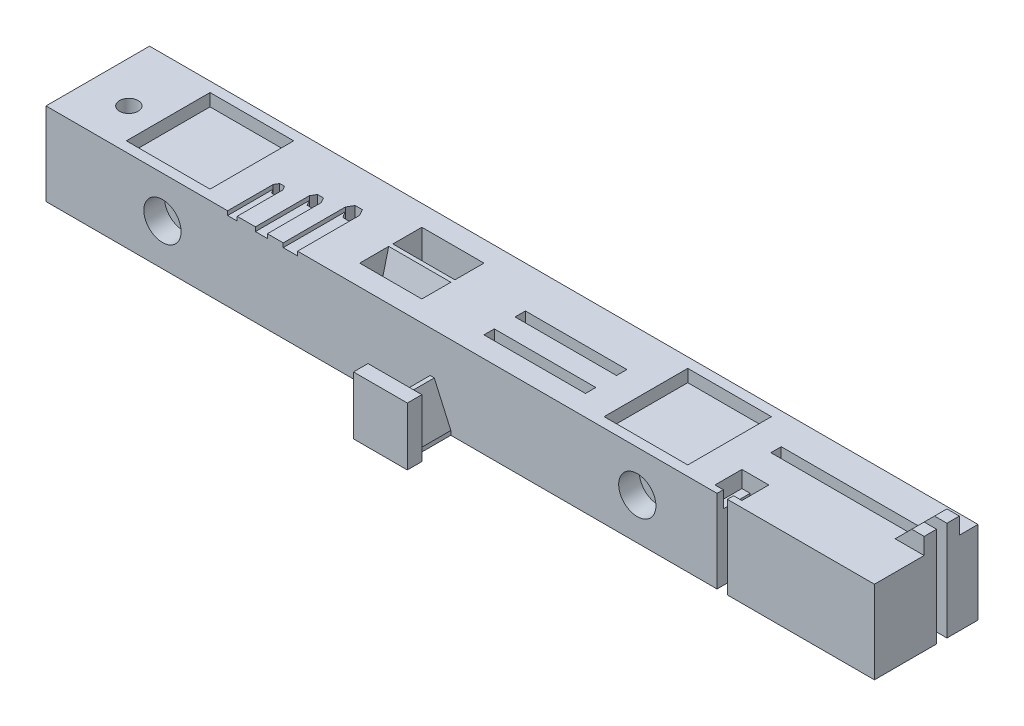
SolidWorks part; units mm, degrees
ref_plane "Piano frontale" through (0, 0, 0) normal (0, 0, 1) x (1, 0, 0)
ref_plane "Piano superiore" through (0, 0, 0) normal (0, 1, 0) x (1, 0, 0)
ref_plane "Piano destro" through (0, 0, 0) normal (1, 0, 0) x (0, 0, -1)
sketch "Schizzo1" plane through (0, 0, 0) normal (0, 0, 1) x (1, 0, 0)
  line L1 (-63.299, 14.3184) -> (136.701, 14.3184)
  line L2 (-63.299, 14.3184) -> (-63.299, -5.6816)
  line L3 (-63.299, -5.6816) -> (136.701, -5.6816)
  line L4 (136.701, 14.3184) -> (136.701, -5.6816)
  dimension "D1" = 20
  dimension "D2" = 200
extrude "Estrusione-Estrusione1" add sketch "Schizzo1" along normal blind 25
sketch "Schizzo2" plane through (0, 14.3184, 0) normal (0, 1, 0) x (1, 0, 0)
  line L0 (136.701, 0) -> (-63.299, 0) construction
  line L1 (136.701, -25) -> (-63.299, -25) construction
  line L2 (-63.299, -25) -> (-63.299, 0) construction
  line L3 (-18.8763, -15) -> (-17.7216, -15)
  line L4 (-17.7216, -15) -> (-17.1443, -14)
  line L5 (-17.1443, -14) -> (-17.7216, -13)
  line L6 (-17.7216, -13) -> (-18.8763, -13)
  line L7 (-18.8763, -13) -> (-19.4537, -14)
  line L8 (-19.4537, -14) -> (-18.8763, -15)
  line L9 (-9.8556, -12) -> (-10.5773, -10.75)
  line L10 (-10.5773, -10.75) -> (-12.0207, -10.75)
  line L11 (-12.0207, -10.75) -> (-12.7423, -12)
  line L12 (-12.7423, -12) -> (-12.0207, -13.25)
  line L13 (-12.0207, -13.25) -> (-10.5773, -13.25)
  line L14 (-10.5773, -13.25) -> (-9.8556, -12)
  line L15 (-3.4329, -11.5) -> (-2.5669, -10)
  line L16 (-2.5669, -10) -> (-3.4329, -8.5)
  line L17 (-3.4329, -8.5) -> (-5.165, -8.5)
  line L18 (-5.165, -8.5) -> (-6.031, -10)
  line L19 (-6.031, -10) -> (-5.165, -11.5)
  line L20 (-5.165, -11.5) -> (-3.4329, -11.5)
  circle A0 centre (-53.299, -15) radius 2.25
  circle A1 centre (-18.299, -14) radius 1 construction
  circle A2 centre (-11.299, -12) radius 1.25 construction
  circle A3 centre (-4.299, -10) radius 1.5 construction
  dimension "D2" = 4.5
  dimension "D4" = 2
  dimension "D5" = 2.5
  dimension "D6" = 3
  dimension "D1" = 15
  dimension "D3" = 10
  dimension "D7" = 35
  dimension "D8" = 7
  dimension "D9" = 7
  dimension "D10" = 11
  dimension "D11" = 13
  dimension "D12" = 15
extrude "Taglio-Estrusione1" cut sketch "Schizzo2" against normal through all
sketch "Schizzo4" plane through (0, 14.3184, 0) normal (0, 1, 0) x (1, 0, 0)
  line L0 (136.701, -25) -> (-63.299, -25) construction
  line L1 (-19.4537, -14) -> (-17.1443, -14)
  line L2 (-19.4537, -14) -> (-19.4537, -25)
  line L3 (-19.4537, -25) -> (-17.1443, -25)
  line L4 (-17.1443, -14) -> (-17.1443, -25)
  line L5 (-12.7423, -12) -> (-9.8556, -12)
  line L6 (-12.7423, -12) -> (-12.7423, -25)
  line L7 (-12.7423, -25) -> (-9.8556, -25)
  line L8 (-9.8556, -12) -> (-9.8556, -25)
  line L10 (-6.031, -10) -> (-2.5669, -10)
  line L11 (-6.031, -10) -> (-6.031, -25)
  line L12 (-6.031, -25) -> (-2.5669, -25)
  line L13 (-2.5669, -10) -> (-2.5669, -25)
extrude "Taglio-Estrusione2" cut sketch "Schizzo4" against normal blind 1
sketch "Schizzo7" plane through (0, 14.3184, 0) normal (0, 1, 0) x (1, 0, 0)
  line L0 (136.701, -25) -> (-2.5669, -25) construction
  line L1 (7.4331, -14.5) -> (22.4331, -14.5)
  line L2 (7.4331, -14.5) -> (7.4331, -20)
  line L3 (7.4331, -20) -> (22.4331, -20)
  line L4 (22.4331, -14.5) -> (22.4331, -20)
  line L5 (7.4331, -5) -> (22.4331, -5)
  line L6 (7.4331, -5) -> (7.4331, -10.5)
  line L7 (7.4331, -10.5) -> (22.4331, -10.5)
  line L8 (22.4331, -5) -> (22.4331, -10.5)
  dimension "D1" = 15
  dimension "D2" = 15
  dimension "D3" = 15
  dimension "D4" = 4
  dimension "D5" = 5.5
  dimension "D6" = 5
  dimension "D7" = 10
extrude "Taglio-Estrusione3" cut sketch "Schizzo7" against normal through all
chamfer "Smusso1" distance 1.5 distance2 6 2 edges at (14.9331, 14.3184, 14.5) (14.9331, 14.3184, 10.5) first distance on face at (14.9331, 14.3184, 7.75)
sketch "Schizzo8" plane through (0, 14.3184, 0) normal (0, 1, 0) x (1, 0, 0)
  line L0 (7.4331, -20) -> (22.4331, -20) construction
  line L1 (37.4331, -17.5) -> (61.9331, -17.5)
  line L2 (37.4331, -17.5) -> (37.4331, -20)
  line L3 (37.4331, -20) -> (61.9331, -20)
  line L4 (61.9331, -17.5) -> (61.9331, -20)
  line L5 (37.4331, -10) -> (61.9331, -10)
  line L6 (37.4331, -10) -> (37.4331, -12.5)
  line L7 (37.4331, -12.5) -> (61.9331, -12.5)
  line L8 (61.9331, -10) -> (61.9331, -12.5)
  line L9 (22.4331, -12) -> (22.4331, -5) construction
  point P10 (22.4331, -8.5)
  dimension "D1" = 24.5
  dimension "D2" = 24.5
  dimension "D3" = 2.5
  dimension "D4" = 2.5
  dimension "D5" = 5
  dimension "D6" = 15
extrude "Taglio-Estrusione4" cut sketch "Schizzo8" against normal blind 15
sketch "Schizzo9" plane through (0, 14.3184, 0) normal (0, 1, 0) x (1, 0, 0)
  line L0 (136.701, -25) -> (136.701, 0) construction
  line L1 (96.701, -7.5) -> (136.701, -7.5)
  line L2 (96.701, -7.5) -> (96.701, -10)
  line L3 (96.701, -10) -> (136.701, -10)
  line L4 (136.701, -7.5) -> (136.701, -10)
  line L5 (136.701, 0) -> (-63.299, 0) construction
  dimension "D1" = 40
  dimension "D2" = 2.5
  dimension "D3" = 7.5
extrude "Taglio-Estrusione5" cut sketch "Schizzo9" against normal through all
sketch "Schizzo10" plane through (0, 14.3184, 0) normal (0, 1, 0) x (1, 0, 0)
  line L1 (136.701, -7.5) -> (129.701, -7.5)
  line L2 (136.701, -7.5) -> (136.701, -4.5)
  line L3 (136.701, -4.5) -> (129.701, -4.5)
  line L4 (129.701, -7.5) -> (129.701, -4.5)
  line L5 (136.701, -10) -> (129.701, -10)
  line L6 (136.701, -10) -> (136.701, -13)
  line L7 (136.701, -13) -> (129.701, -13)
  line L8 (129.701, -10) -> (129.701, -13)
  dimension "D1" = 7
  dimension "D2" = 7
  dimension "D3" = 3
  dimension "D4" = 3
extrude "Estrusione-Estrusione5" add sketch "Schizzo10" along normal blind 4
chamfer "Smusso2" distance 4 angle 45 2 edges at (129.701, 18.3184, 11.5) (129.701, 18.3184, 6)
sketch "Schizzo11" plane through (0, 14.3184, 0) normal (0, 1, 0) x (1, 0, 0)
  line L0 (136.701, -25) -> (-2.5669, -25) construction
  line L1 (98.701, -25) -> (101.201, -25)
  line L2 (98.701, -25) -> (98.701, -17)
  line L3 (98.701, -17) -> (101.201, -17)
  line L4 (101.201, -25) -> (101.201, -17)
  line L5 (96.701, -7.5) -> (96.701, -10) construction
  dimension "D1" = 2.5
  dimension "D2" = 8
  dimension "D3" = 2
extrude "Taglio-Estrusione6" cut sketch "Schizzo11" against normal through all
sketch "Schizzo12" plane through (0, 14.3184, 0) normal (0, 1, 0) x (1, 0, 0)
  line L0 (101.201, -17) -> (98.701, -17) construction
  line L1 (96.701, -17) -> (103.201, -17)
  line L2 (96.701, -17) -> (96.701, -23.5)
  line L3 (96.701, -23.5) -> (103.201, -23.5)
  line L4 (103.201, -17) -> (103.201, -23.5)
  line L7 (96.701, -7.5) -> (96.701, -10) construction
  dimension "D1" = 6.5
  dimension "D2" = 6.5
extrude "Taglio-Estrusione7" cut sketch "Schizzo12" against normal blind 4
sketch "Schizzo13" plane through (0, 0, 25) normal (0, 0, 1) x (1, 0, 0)
  line L0 (-63.299, -5.6816) -> (98.701, -5.6816) construction
  line L1 (25.4331, 4.3184) -> (34.4331, 4.3184)
  line L2 (25.4331, 4.3184) -> (25.4331, -5.6816)
  line L3 (25.4331, -5.6816) -> (34.4331, -5.6816)
  line L4 (34.4331, 4.3184) -> (34.4331, -5.6816)
  dimension "D1" = 10
  dimension "D2" = 3
  dimension "D3" = 9
extrude "Estrusione-Estrusione9" add sketch "Schizzo13" along normal blind 9 contours L2 L3 L4 L1
sketch "Schizzo14" plane through (0, 0, 34) normal (0, 0, 1) x (1, 0, 0)
  line L0 (25.4331, -5.6816) -> (34.4331, -5.6816) construction
  line L1 (23.4331, 8.3184) -> (36.4331, 8.3184)
  line L2 (23.4331, 8.3184) -> (23.4331, -5.6816)
  line L3 (23.4331, -5.6816) -> (36.4331, -5.6816)
  line L4 (36.4331, 8.3184) -> (36.4331, -5.6816)
  line L5 (25.4331, 4.3184) -> (25.4331, -5.6816) construction
  dimension "D1" = 13
  dimension "D2" = 14
  dimension "D3" = 2
extrude "Estrusione-Estrusione10" add sketch "Schizzo14" along normal blind 3.5
chamfer "Smusso3" distance 9 distance2 4 1 edges at (34.4331, 4.3184, 29.5) first distance on face at (34.4331, 0.5684, 30.625)
chamfer "Smusso4" distance 4 distance2 9 1 edges at (25.4331, 4.3184, 29.5) first distance on face at (27.9331, 4.3184, 29.5)
sketch "Schizzo16" plane through (0, 0, 25) normal (0, 0, 1) x (1, 0, 0)
  line L2 (-19.4537, 14.3184) -> (-63.299, 14.3184) construction
  line L3 (98.701, 14.3184) -> (-2.5669, 14.3184) construction
  circle A0 centre (-35.179, 4.3184) radius 2.25
  circle A1 centre (79.451, 4.3184) radius 2.25
  dimension "D3" = 4.5
  dimension "D4" = 4.5
  dimension "D1" = 17.25
  dimension "D2" = 15.87
  dimension "D5" = 10
  dimension "D6" = 10
extrude "Taglio-Estrusione8" cut sketch "Schizzo16" against normal through all
sketch "Schizzo17" plane through (0, 0, 25) normal (0, 0, 1) x (1, 0, 0)
  circle A0 centre (-35.179, 4.3184) radius 4.5
  circle A1 centre (79.451, 4.3184) radius 4.5
  dimension "D1" = 9
  dimension "D2" = 9
extrude "Taglio-Estrusione9" cut sketch "Schizzo17" against normal blind 5
sketch "Schizzo18" plane through (0, 14.3184, 0) normal (0, 1, 0) x (1, 0, 0)
  line L0 (136.701, 0) -> (-63.299, 0) construction
  line L1 (69.0331, -2.4) -> (89.2331, -2.4)
  line L2 (69.0331, -2.4) -> (69.0331, -22.6)
  line L3 (69.0331, -22.6) -> (89.2331, -22.6)
  line L4 (89.2331, -2.4) -> (89.2331, -22.6)
  line L5 (61.9331, -20) -> (61.9331, -17.5) construction
  line L10 (-46.299, -2.4) -> (-26.099, -2.4)
  line L11 (-46.299, -2.4) -> (-46.299, -22.6)
  line L12 (-46.299, -22.6) -> (-26.099, -22.6)
  line L13 (-26.099, -2.4) -> (-26.099, -22.6)
  circle A0 centre (-53.299, -15) radius 2.25 construction
  dimension "D8" = 7
  dimension "D1" = 20.2
  dimension "D2" = 20.2
  dimension "D3" = 2.4
  dimension "D4" = 7.1
  dimension "D5" = 20.2
  dimension "D6" = 20.2
  dimension "D7" = 2.4
extrude "Taglio-Estrusione10" cut sketch "Schizzo18" against normal blind 3
